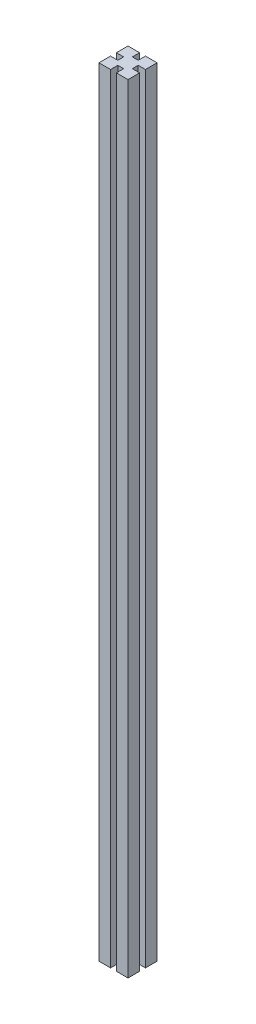
SolidWorks part; units mm, degrees
ref_plane "Front Plane" through (0, 0, 0) normal (0, 0, 1) x (1, 0, 0)
ref_plane "Top Plane" through (0, 0, 0) normal (0, 1, 0) x (1, 0, 0)
ref_plane "Right Plane" through (0, 0, 0) normal (1, 0, 0) x (0, 0, -1)
sketch "Sketch1" plane through (0, 0, 0) normal (0, 1, 0) x (1, 0, 0)
  line L0 (0, 12.5) -> (0, -25) construction
  line L1 (-25, 25) -> (-5, 25)
  line L2 (-25, 25) -> (-25, 5)
  line L3 (-25, -25) -> (-5, -25)
  line L4 (25, 25) -> (25, 5)
  line L5 (-25, 25) -> (25, -25) construction
  line L6 (-25, -25) -> (25, 25) construction
  line L7 (-25, 0) -> (12.5, 0) construction
  line L8 (-5, 25) -> (-5, 12.5)
  line L9 (-5, 12.5) -> (5, 12.5)
  line L10 (-5, -12.5) -> (5, -12.5)
  line L11 (-5, -25) -> (-5, -12.5)
  line L12 (-25, 5) -> (-12.5, 5)
  line L13 (-12.5, 5) -> (-12.5, -5)
  line L14 (12.5, 5) -> (12.5, -5)
  line L15 (25, 5) -> (12.5, 5)
  line L16 (25, -5) -> (12.5, -5)
  line L17 (-25, -5) -> (-12.5, -5)
  line L18 (5, -25) -> (5, -12.5)
  line L19 (5, 25) -> (5, 12.5)
  line L20 (5, 25) -> (25, 25)
  line L21 (25, -5) -> (25, -25)
  line L22 (5, -25) -> (25, -25)
  line L23 (-25, -5) -> (-25, -25)
  point P0 (0, 0)
  point P24 (12.5, 0)
  point P25 (-12.5, 0)
  point P28 (0, -12.5)
  point P29 (0, 12.5)
  dimension "D1" = 50
  dimension "D2" = 10
  dimension "D3" = 12.5
  dimension "D4" = 50
extrude "Boss-Extrude1" add sketch "Sketch1" along normal blind 1338
extrude "Boss-Extrude2" add sketch "Sketch1<2>" along normal blind 10
sketch "Sketch1<2>" plane through (0, 0, 0) normal (0, 1, 0) x (1, 0, 0) same geometry as "Sketch1"
